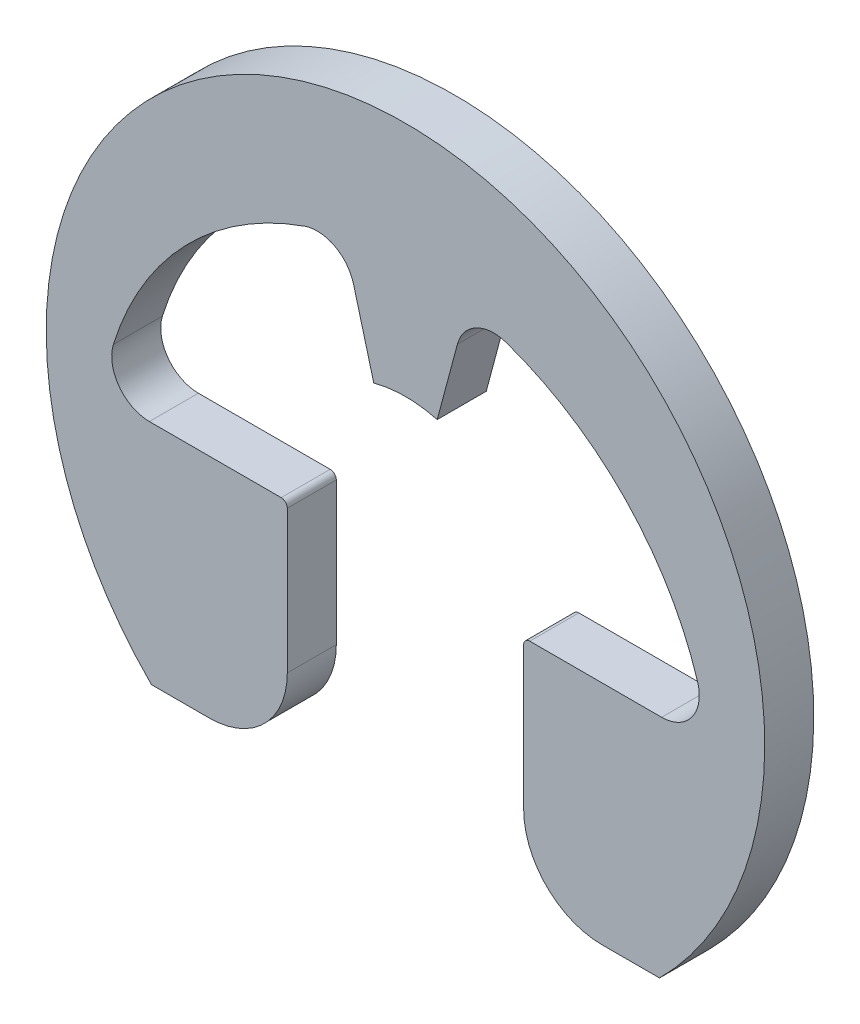
SolidWorks part; units mm, degrees
ref_plane "Plane1" through (0, 0, 0) normal (0, 0, 1) x (1, 0, 0)
ref_plane "Plane2" through (0, 0, 0) normal (0, 1, 0) x (1, 0, 0)
ref_plane "Plane3" through (0, 0, 0) normal (1, 0, 0) x (0, 0, -1)
sketch "Clipboard" plane through (0, 0, 0) normal (0, 0, 1) x (1, 0, 0)
  line L0 (0, 0) -> (1.5, 0)
  circle A0 centre (0, 0) radius 1.45
  circle A1 centre (0, 0) radius 4.25
sketch "BodySke" plane through (0, 0, 0) normal (0, 0, 1) x (1, 0, 0)
  line L0 (-3.6466, 0) -> (3.6466, 0) construction
  line L1 (0, 0) -> (0, 2.8966) construction
  line L2 (0, 0) -> (0.1962, 0.7323) construction
  line L3 (0, 0) -> (4.2467, -1.1379) construction
  line L4 (0, 0) -> (-0.1962, 0.7323) construction
  line L5 (0, 0) -> (-4.2467, -1.1379) construction
  line L6 (0, 0) -> (3.1088, -3.1088) construction
  line L7 (0, 0) -> (-3.1088, -3.1088) construction
  line L8 (3.1088, -3.1088) -> (2.4022, -3.1088)
  line L9 (-2.4022, -3.1088) -> (-3.1088, -3.1088)
  line L10 (1.5213, -0.3326) -> (3.1346, -0.3326)
  line L11 (0.6356, 2.372) -> (0.3882, 1.4489)
  line L12 (-0.6356, 2.372) -> (-0.3882, 1.4489)
  line L13 (1.4463, -0.4076) -> (1.4463, -2.153)
  line L14 (-1.5213, -0.3326) -> (-3.1346, -0.3326)
  line L15 (-1.4463, -0.4076) -> (-1.4463, -2.153)
  circle A0 centre (0, 0) radius 1.5 construction
  arc A1 (3.6466, 0) -> (-3.6466, 0) centre (0, -0.8471) ccw construction
  arc A2 (3.1088, -3.1088) -> (-3.1088, -3.1088) centre (0, 0) ccw
  arc A3 (1.5213, -0.3326) -> (1.4463, -0.4076) centre (1.5213, -0.4076) ccw
  arc A4 (-1.4463, -0.4076) -> (-1.5213, -0.3326) centre (-1.5213, -0.4076) ccw
  arc A5 (-3.5746, 0.2651) -> (-1.2324, 2.6879) centre (0, -0.8471) cw
  arc A6 (-0.3882, 1.4489) -> (0.3882, 1.4489) centre (0, 0) cw
  arc A7 (1.2324, 2.6879) -> (3.5746, 0.2651) centre (0, -0.8471) cw
  arc A8 (3.1346, -0.3326) -> (3.5746, 0.2651) centre (3.1346, 0.1282) ccw
  arc A9 (1.2324, 2.6879) -> (0.6356, 2.372) centre (1.0807, 2.2527) ccw
  arc A10 (-0.6356, 2.372) -> (-1.2324, 2.6879) centre (-1.0807, 2.2527) ccw
  arc A11 (-3.5746, 0.2651) -> (-3.1346, -0.3326) centre (-3.1346, 0.1282) ccw
  arc A12 (1.4463, -2.153) -> (2.4022, -3.1088) centre (2.4022, -2.153) ccw
  arc A13 (-2.4022, -3.1088) -> (-1.4463, -2.153) centre (-2.4022, -2.153) ccw
  dimension "CavityFilletRad" = 0.4609
  dimension "D3" = 30
  dimension "D1" = 15
  dimension "CavityWidth" = 7.2931
extrude "Body" add sketch "BodySke" against normal blind 0.6
equation "' \"FreeID@Clipboard\" = 2.9"
equation "' \"Thickness@Body\" = 0.6"
equation "' \"GrooveDia@BodySke\" = 3.0"
equation "' \"FreeOD@Clipboard\" = 8.5"
equation "' \"LargeSection@Clipboard\" = 1.5"
equation "' \"FreeID@Clipboard\" = 11.5"
equation "' \"Thickness@Body\" = 1.1"
equation "' \"GrooveDia@BodySke\" = 11.8"
equation "' \"FreeOD@Clipboard\" = 23.2"
equation "' \"LargeSection@Clipboard\" = 3.9"
equation "\"OutsideDia@BodySke\" = ( \"GrooveDia@BodySke\"  /  \"FreeID@Clipboard\" )  * \"FreeOD@Clipboard\""
equation "\"CavityHeight@BodySke\" = \"OutsideDia@BodySke\"  /  2 - \"LargeSection@Clipboard\""
equation "\"CavityWidth@BodySke\" = \"OutsideDia@BodySke\" -  \"LargeSection@Clipboard\""
equation "\"CavityFilletRad@BodySke\" =  (\"CavityHeight@BodySke\" * 2 - \"GrooveDia@BodySke\") / 2 * 0.33"
equation "\"InnerTipRad@BodySke\" = \"GrooveDia@BodySke\" * 0.025"
equation "\"OuterTipRadius@BodySke\" =  (\"OutsideDia@BodySke\" - \"GrooveDia@BodySke\") / 2 * 0.33"
